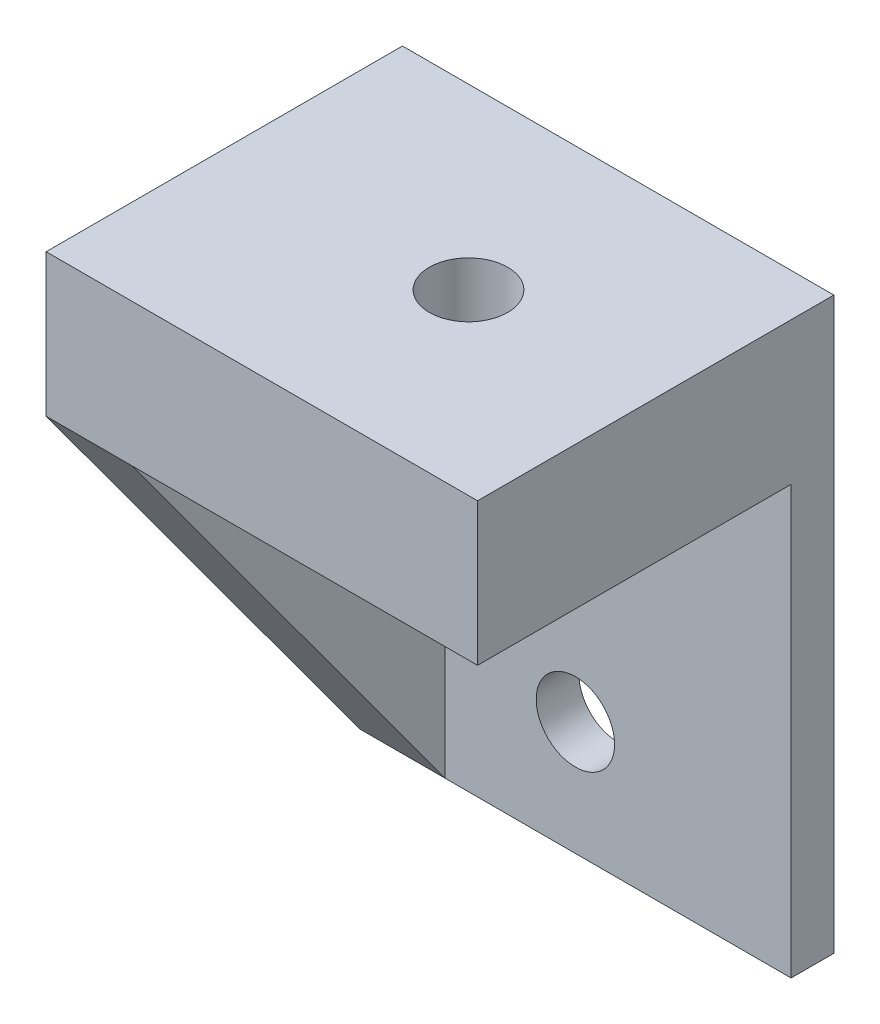
SolidWorks part; units mm, degrees
ref_plane "Front" through (0, 0, 0) normal (0, 0, 1) x (1, 0, 0)
ref_plane "Top" through (0, 0, 0) normal (0, 1, 0) x (1, 0, 0)
ref_plane "Right" through (0, 0, 0) normal (1, 0, 0) x (0, 0, -1)
sketch "Sketch1" plane through (0, 0, 0) normal (0, 1, 0) x (1, 0, 0)
  line L1 (0, 0) -> (15.135, 0)
  line L2 (0, 0) -> (0, 12.5)
  line L3 (0, 12.5) -> (15.135, 12.5)
  line L4 (15.135, 0) -> (15.135, 12.5)
  dimension "D1" = 15.135
  dimension "D2" = 12.5
extrude "base" add sketch "Sketch1" along normal blind 5
sketch "Sketch2" plane through (0, 0, -12.5) normal (0, 0, -1) x (-1, 0, 0)
  line L0 (0, 5) -> (0, 0) construction
  line L1 (-15.135, 0) -> (0, 0)
  line L2 (-15.135, 0) -> (-15.135, -15)
  line L3 (-15.135, -15) -> (0, -15)
  line L4 (0, 0) -> (0, -15)
  dimension "D1" = 15
extrude "Boss-Extrude2" add sketch "Sketch2" against normal blind 1.5
sketch "Sketch3" plane through (0, 0, 0) normal (-1, 0, 0) x (0, 0, 1)
  line L0 (0, 0) -> (-11, -15)
  line L1 (-11, -15) -> (-11, 0)
  line L2 (-11, 0) -> (0, 0)
extrude "Boss-Extrude3" add sketch "Sketch3" against normal up to surface (15.135 mm away) up to face at (15.135, -3.3333, -7.8333)
sketch "Sketch4" plane through (0, 0, 0) normal (0, 0, 1) x (1, 0, 0)
  line L0 (15.135, -15) -> (0, -15) construction
  line L1 (3, 0) -> (12.135, 0)
  line L2 (3, 0) -> (3, -15)
  line L3 (3, -15) -> (12.135, -15)
  line L4 (12.135, 0) -> (12.135, -15)
  line L5 (0, 0) -> (15.135, 0) construction
  line L6 (15.135, 0) -> (15.135, -15) construction
  point P6 (7.5675, 0)
  point P9 (7.5675, 0)
  dimension "D1" = 3
extrude "Cut-Extrude1" cut sketch "Sketch4" against normal up to vertex (11 mm away) up to point (15.135, -15, -11)
sketch "Sketch5" plane through (0, 0, -11) normal (0, 0, 1) x (1, 0, 0)
  line L0 (12.135, 0) -> (3, 0) construction
  line L1 (3, -15) -> (12.135, -15) construction
  circle A0 centre (7.5675, -4) radius 2.3 construction
  circle A1 centre (7.5675, -11) radius 2.3 construction
  circle A2 centre (7.5675, -4) radius 1.375
  circle A3 centre (7.5675, -11) radius 1.375
  point P8 (7.5675, 0)
  dimension "D1" = 4.6
  dimension "D4" = 2.75
  dimension "D2" = 4
  dimension "D3" = 4
extrude "Cut-Extrude2" cut sketch "Sketch5" against normal blind 2
sketch "Sketch6" plane through (0, 5, 0) normal (0, 1, 0) x (1, 0, 0)
  line L0 (0, 12.5) -> (0, 0) construction
  line L1 (0, 0) -> (15.135, 0) construction
  circle A0 centre (8.5675, 6.25) radius 1.375
  dimension "D1" = 2.75
  dimension "D2" = 8.5675
  dimension "D3" = 6.25
extrude "Cut-Extrude3" cut sketch "Sketch6" against normal blind 5.75
sketch "Sketch7" plane through (12.135, 0, 0) normal (-1, 0, 0) x (0, 0, 1)
  line L3 (-11, -15) -> (0, 0)
  line L4 (0, 0) -> (-11, 0)
  line L5 (-11, 0) -> (-11, -15)
  line L6 (-11, -15) -> (0, 0)
  line L7 (0, 0) -> (-11, 0)
  line L8 (-11, 0) -> (-11, -15)
  dimension "D1" = 0
extrude "Cut-Extrude4" cut sketch "Sketch7" against normal blind 10
